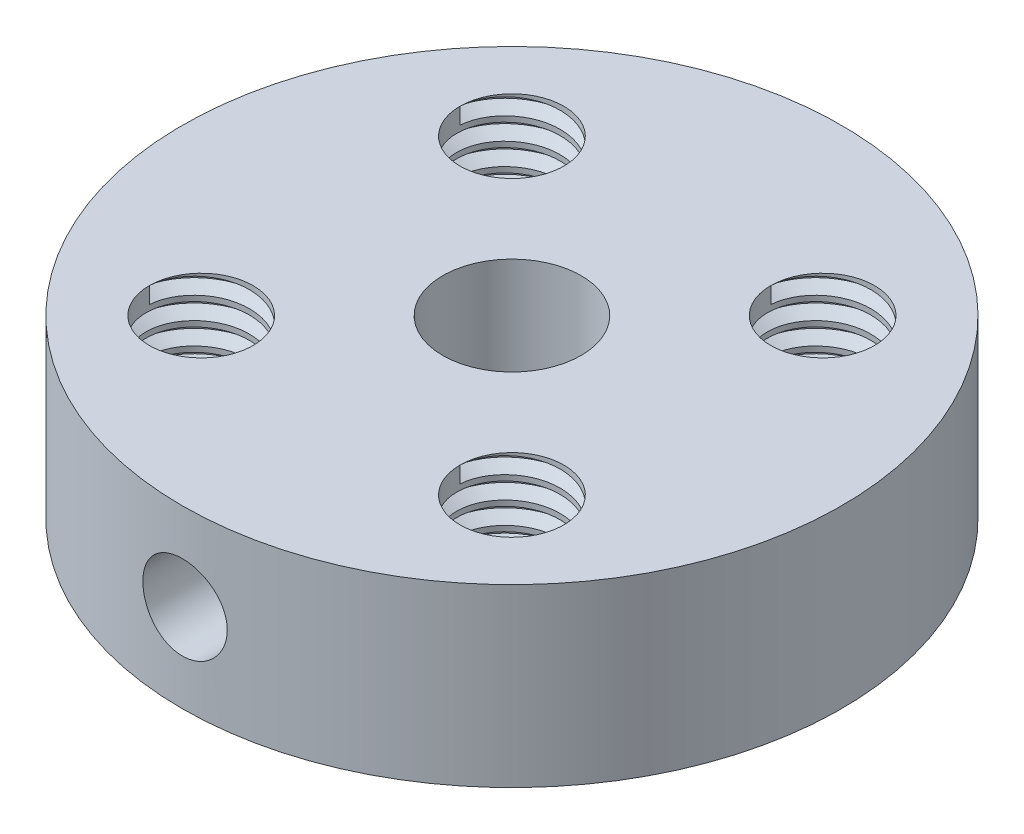
SolidWorks part; units mm, degrees
material "Plain Carbon Steel"
ref_plane "Front Plane" through (0, 0, 0) normal (0, 0, 1) x (1, 0, 0)
ref_plane "Top Plane" through (0, 0, 0) normal (0, 1, 0) x (1, 0, 0)
ref_plane "Right Plane" through (0, 0, 0) normal (1, 0, 0) x (0, 0, -1)
sketch "Sketch1" plane through (0, 0, 0) normal (0, 1, 0) x (1, 0, 0)
  circle A0 centre (0, 0) radius 9.525
  circle A1 centre (0, 0) radius 2
  dimension "D1" = 19.05
  dimension "D2" = 4
extrude "Boss-Extrude1" add sketch "Sketch1" along normal blind 5.08
ref_plane "Plane2" through (0, 0, 9.525) normal (0, 0, 1) x (1, 0, 0)
ref_point "Point1"
sketch "Sketch2" plane through (0, 0, 9.525) normal (0, 0, 1) x (1, 0, 0)
  line L0 (0, -8.1196) -> (0, 8.1196) construction
  circle A1 centre (0, 2.54) radius 1.2192
  point P7 (0, 0)
  point P11 (0, 4)
  point P14 (0, 0)
  dimension "D1" = 2.4384
sketch "Sketch4" plane through (0, 5.08, 0) normal (0, 1, 0) x (1, 0, 0)
  line L0 (0, 0) -> (3.7248, 3.7248) construction
  line L1 (-4.7829, 0) -> (4.7829, 0) construction
  circle A0 centre (0, 0) radius 5.6 construction
  circle A1 centre (0, 0) radius 6.35 construction
  circle A2 centre (4.4901, 4.4901) radius 1.5
  circle A3 centre (4.4901, -4.4901) radius 1.5
  circle A4 centre (-4.4901, -4.4901) radius 1.5
  circle A5 centre (-4.4901, 4.4901) radius 1.5
  point P9 (0, 0)
  point P20 (0.9546, 0)
  point P21 (0, 0)
  dimension "D3" = 3
  dimension "D5" = 12.7
  dimension "D2" = 45
  dimension "D1" = 0.75
  dimension "D4" = 4
extrude "Cut-Extrude3" cut sketch "Sketch2" against normal up to surface (7.9396 mm away) up to face at (0, 5.08, 2)
extrude "Cut-Extrude4" cut sketch "Sketch4" against normal up to surface (5.08 mm away) up to face at (0, 0, 9.525)
thread "Thread2" pitch 0.635 method cut profile "Thread Profile2" start angle 0, offset 0, length 0, pitch 0.635, diameter 3
ref_plane "Plane4" through (2.9901, 5.08, -4.4901) normal (0, 0, 1) x (-1, 0, 0)
sketch "Thread Profile2" plane through (2.9901, 5.08, -4.4901) normal (0, 0, 1) x (-1, 0, 0)
  line L0 (0, 0) -> (0, 0.635) construction
  line L1 (0, 0) -> (0.3437, 0.1984)
  line L2 (0.3437, 0.1984) -> (0.3437, 0.2778)
  line L3 (0.3437, 0.2778) -> (0, 0.4762)
  line L4 (0.3437, 0.2381) -> (0, 0.2381) construction
  line L11 (0, 0) -> (0, 0.4762)
  point P2 (0, 0)
  dimension "Pitch" = 0.635
  dimension "Profile_Angle" = 60
  dimension "Profile_Land" = 0.0794
  dimension "Profile_Height" = 0.3437
thread "Thread3" pitch 0.635 method cut profile "Thread Profile3" start angle 0, offset 0, length 0, pitch 0.635, diameter 3
ref_plane "Plane5" through (2.9901, 5.08, 4.4901) normal (0, 0, 1) x (-1, 0, 0)
sketch "Thread Profile3" plane through (2.9901, 5.08, 4.4901) normal (0, 0, 1) x (-1, 0, 0)
  line L0 (0, 0) -> (0, 0.635) construction
  line L1 (0, 0) -> (0.3437, 0.1984)
  line L2 (0.3437, 0.1984) -> (0.3437, 0.2778)
  line L3 (0.3437, 0.2778) -> (0, 0.4762)
  line L4 (0.3437, 0.2381) -> (0, 0.2381) construction
  line L11 (0, 0) -> (0, 0.4762)
  point P2 (0, 0)
  dimension "Pitch" = 0.635
  dimension "Profile_Angle" = 60
  dimension "Profile_Land" = 0.0794
  dimension "Profile_Height" = 0.3437
thread "Thread4" pitch 0.635 method cut profile "Thread Profile4" start angle 0, offset 0, length 0, pitch 0.635, diameter 3
ref_plane "Plane6" through (-5.9901, 5.08, 4.4901) normal (0, 0, 1) x (-1, 0, 0)
sketch "Thread Profile4" plane through (-5.9901, 5.08, 4.4901) normal (0, 0, 1) x (-1, 0, 0)
  line L0 (0, 0) -> (0, 0.635) construction
  line L1 (0, 0) -> (0.3437, 0.1984)
  line L2 (0.3437, 0.1984) -> (0.3437, 0.2778)
  line L3 (0.3437, 0.2778) -> (0, 0.4762)
  line L4 (0.3437, 0.2381) -> (0, 0.2381) construction
  line L11 (0, 0) -> (0, 0.4762)
  point P2 (0, 0)
  dimension "Pitch" = 0.635
  dimension "Profile_Angle" = 60
  dimension "Profile_Land" = 0.0794
  dimension "Profile_Height" = 0.3437
thread "Thread5" pitch 0.635 method cut profile "Thread Profile5" start angle 0, offset 0, length 0, pitch 0.635, diameter 3
ref_plane "Plane7" through (-5.9901, 5.08, -4.4901) normal (0, 0, 1) x (-1, 0, 0)
sketch "Thread Profile5" plane through (-5.9901, 5.08, -4.4901) normal (0, 0, 1) x (-1, 0, 0)
  line L0 (0, 0) -> (0, 0.635) construction
  line L1 (0, 0) -> (0.3437, 0.1984)
  line L2 (0.3437, 0.1984) -> (0.3437, 0.2778)
  line L3 (0.3437, 0.2778) -> (0, 0.4762)
  line L4 (0.3437, 0.2381) -> (0, 0.2381) construction
  line L11 (0, 0) -> (0, 0.4762)
  point P2 (0, 0)
  dimension "Pitch" = 0.635
  dimension "Profile_Angle" = 60
  dimension "Profile_Land" = 0.0794
  dimension "Profile_Height" = 0.3437
